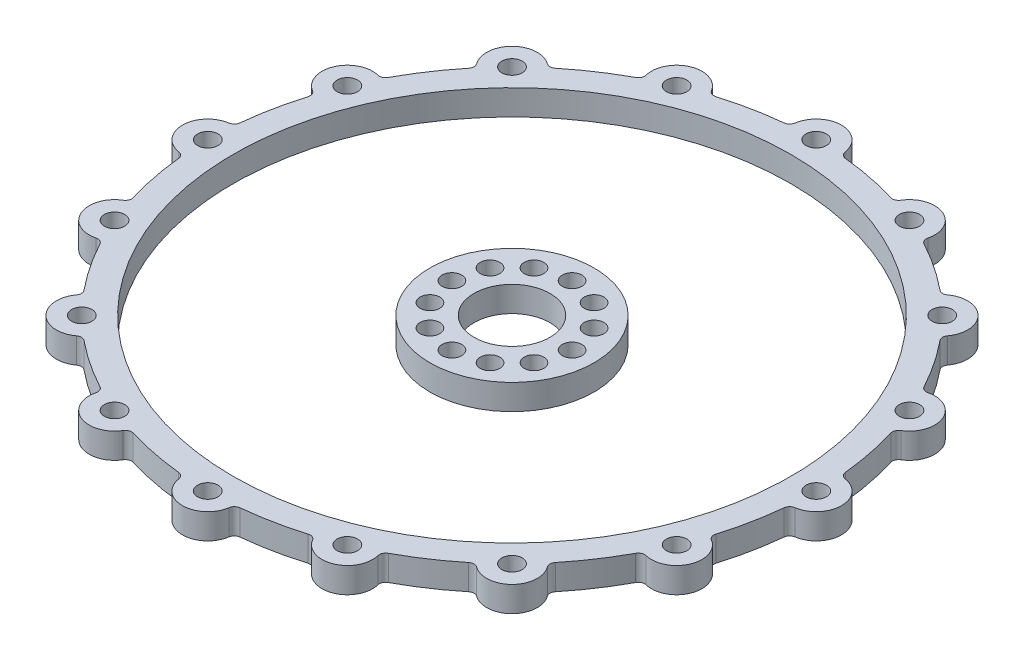
SolidWorks part; units mm, degrees
ref_plane "Front Plane" through (0, 0, 0) normal (0, 0, 1) x (1, 0, 0)
ref_plane "Top Plane" through (0, 0, 0) normal (0, 1, 0) x (1, 0, 0)
ref_plane "Right Plane" through (0, 0, 0) normal (1, 0, 0) x (0, 0, -1)
sketch "Sketch1" plane through (0, 0, 0) normal (0, 1, 0) x (1, 0, 0)
  circle A0 centre (0, 0) radius 76.2
  circle A1 centre (0, 0) radius 9.525
  dimension "D1" = 152.4
  dimension "D2" = 19.05
extrude "Boss-Extrude1" add sketch "Sketch1" along normal blind 6.35
sketch "Sketch2" plane through (0, 6.35, 0) normal (0, 1, 0) x (1, 0, 0)
  circle A0 centre (0, 0) radius 76.2 construction
  arc A1 (6.3445, 75.9354) -> (-6.3445, 75.9354) centre (0, 0) ccw
  arc A2 (6.3445, 75.9354) -> (-6.3445, 75.9354) centre (0, 76.2) ccw
  dimension "D1" = 12.7
extrude "Boss-Extrude3" add sketch "Sketch2" against normal through all
fillet "Fillet1" radius 1.5875 2 edges at (6.3445, 3.175, -75.9354) (-6.3445, 3.175, -75.9354)
hole_wizard "#10 Clearance Hole1" positions "Sketch3" profile "Sketch5" hole size "#10" standard "ANSI Inch"
sketch "Sketch3" plane through (0, 6.35, 0) normal (0, 1, 0) x (1, 0, 0)
  circle A0 centre (0, 0) radius 76.2 construction
  point P4 (0, 76.2)
  dimension "D1" = 152.4
sketch "Sketch5" plane through (0, 6.35, -76.2) normal (1, 0, 0) x (0, 0, 1)
  line L0 (0, 0) -> (0, 8.1378)
  line L1 (0, 8.1378) -> (2.5527, 6.604)
  line L2 (2.5527, 6.604) -> (2.5527, 0)
  line L5 (2.5527, 0) -> (0, 0)
  line L10 (0, 8.1378) -> (-2.5527, 6.604) construction
  line L11 (0, -6.35) -> (0, 107.95) construction
  dimension "Hole Dia." = 5.1054
  dimension "Hole Depth" = 6.604
  dimension "Drill Angle" = 118
pattern_circular "CirPattern1" count 16 over 360 about axis through (0, 6.35, 0) along (0, -1, 0) of "Boss-Extrude3", "Fillet1", "#10 Clearance Hole1" reverse direction yes
hole_wizard "#10 (0.1935) Diameter Hole1" positions "Sketch6" profile "Sketch7" hole size "#10" standard "ANSI Inch"
sketch "Sketch6" plane through (0, 6.35, 0) normal (0, 1, 0) x (1, 0, 0)
  circle A0 centre (0, 0) radius 15.0495
  point P5 (0, 15.0495)
  dimension "D1" = 30.099
sketch "Sketch7" plane through (0, 6.35, -15.0495) normal (1, 0, 0) x (0, 0, 1)
  line L0 (0, 0) -> (0, 13.4146)
  line L1 (0, 13.4146) -> (2.4574, 11.938)
  line L2 (2.4574, 11.938) -> (2.4574, 0)
  line L5 (2.4574, 0) -> (0, 0)
  line L10 (0, 13.4146) -> (-2.4575, 11.938) construction
  line L11 (0, -6.35) -> (0, 107.95) construction
  dimension "Hole Dia." = 4.9149
  dimension "Hole Depth" = 11.938
  dimension "Drill Angle" = 118
pattern_circular "CirPattern2" count 12 over 360 about axis through (0, 6.35, 0) along (0, -1, 0) of "#10 (0.1935) Diameter Hole1" reverse direction yes
sketch "Sketch8" plane through (0, 6.35, 0) normal (0, 1, 0) x (1, 0, 0)
  line L0 (0, 9.525) -> (0, 15.0495) construction
  line L1 (0, 15.0495) -> (0, 20.574) construction
  line L2 (0, 20.574) -> (0, 69.85) construction
  line L3 (17.8176, -10.287) -> (60.4919, -34.925) construction
  line L4 (0, 55.0158) -> (0, 26.924)
  line L5 (15.5136, 52.7832) -> (8.7884, 29.9014)
  line L6 (17.0132, 26.1128) -> (30.0325, 46.0954)
  line L7 (41.8119, 35.7561) -> (23.6862, 20.2556)
  line L8 (28.5094, 12.5914) -> (50.3259, 22.2269)
  line L9 (54.5513, 7.1338) -> (30.903, 4.0413)
  line L10 (30.7603, -5.0131) -> (68.9404, -11.2355)
  line L11 (25.8551, 7.5111) -> (29.9288, 8.6945) construction
  line L12 (54.9463, 2.7641) -> (59.183, 2.9772) construction
  line L13 (59.183, 2.9772) -> (63.4198, 3.1903) construction
  line L14 (17.8499, 20.1565) -> (13.64, 15.4026) construction
  line L15 (54.2448, 33.0114) -> (59.6693, 36.3126) construction
  line L16 (0, 26.924) -> (0, 20.574)
  line L17 (0, 20.574) -> (0, 19.5016)
  circle A0 centre (0, 0) radius 69.85 construction
  arc A1 (6.2782, 77.1525) -> (-6.2782, 77.1525) centre (0, 76.2) ccw construction
  arc A2 (6.2782, 77.1525) -> (-6.2782, 77.1525) centre (0, 76.2) ccw construction
  arc A3 (-6.2782, 77.1525) -> (6.2782, 77.1525) centre (0, 76.2) ccw construction
  arc A4 (6.2782, 77.1525) -> (7.6875, 75.8112) centre (7.8477, 77.3906) ccw construction
  circle A5 centre (0, 0) radius 9.525 construction
  circle A6 centre (0, 0) radius 20.574 construction
  circle A7 centre (0, 0) radius 55.0158 construction
  arc A8 (15.5136, 52.7832) -> (0, 55.0158) centre (7.9174, 55.0158) ccw
  arc A9 (8.7884, 29.9014) -> (17.0132, 26.1128) centre (13.179, 28.6109) ccw
  arc A10 (30.0325, 46.0954) -> (41.8119, 35.7561) centre (36.6662, 41.7733) cw
  arc A11 (28.5094, 12.5914) -> (23.6862, 20.2556) centre (26.6605, 16.7776) cw
  arc A12 (54.5513, 7.1338) -> (50.3259, 22.2269) centre (53.5247, 14.9844) ccw
  arc A13 (30.903, 4.0413) -> (30.7603, -5.0131) centre (31.4964, -0.4964) ccw
  circle A14 centre (0, 0) radius 26.924 construction
  circle A15 centre (0, 0) radius 31.1661 construction
  circle A16 centre (0, 0) radius 63.5 construction
  dimension "D4" = 6.35
  dimension "D1" = 120
sketch "Sketch9" plane through (0, 6.35, 0) normal (0, 1, 0) x (1, 0, 0)
  circle A0 centre (0, 0) radius 69.85
  circle A1 centre (0, 0) radius 20.574
extrude "Cut-Extrude1" cut sketch "Sketch9" against normal through all
sketch "Sketch12" plane through (0, 6.35, 0) normal (0, 1, 0) x (1, 0, 0)
  line L2 (20.574, 0) -> (37.5959, 0) construction
  line L3 (37.5959, 0) -> (46.8121, 23.5035) construction
  line L4 (46.8121, 23.5035) -> (38.1661, 38.1661) construction
  line L5 (38.1661, 38.1661) -> (29.5201, 52.8286) construction
  line L6 (29.5201, 52.8286) -> (3.0118, 58.6502) construction
  line L7 (3.0118, 58.6502) -> (-17.3746, 47.7364) construction
  line L8 (37.5959, 0) -> (28.9498, 14.6625) construction
  line L9 (47.1981, -180.1465) -> (-7.2452, -802.4361) construction
  line L10 (28.9498, 14.6625) -> (20.3038, 29.3251) construction
  line L11 (20.3038, 29.3251) -> (11.6578, 43.9876) construction
  line L12 (11.6578, 43.9876) -> (3.0118, 58.6502) construction
  line L13 (38.1661, 38.1661) -> (0, 0) construction
  line L14 (0, 0) -> (-17.3746, 47.7364) construction
  line L15 (-1000, 0) -> (49000, 0) construction
  line L19 (-68.7888, 12.1293) -> (-52.0256, 9.1735) construction
  line L20 (-52.0256, 9.1735) -> (-37.761, 36.8226) construction
  line L21 (-37.761, 36.8226) -> (-17.3746, 47.7364) construction
  line L22 (29.5201, 52.8286) -> (9.1337, 41.9148) construction
  line L23 (9.1337, 41.9148) -> (-11.2527, 31.0011) construction
  line L24 (-11.2527, 31.0011) -> (-31.6392, 20.0873) construction
  line L26 (-31.6392, 20.0873) -> (-52.0256, 9.1735) construction
  arc A0 (1.1221, 5.0617) -> (-1.7732, 4.8719) centre (0, 0) ccw construction
  arc A1 (1.1221, 5.0617) -> (3.6661, 3.6661) centre (0, 0) cw construction
  circle A3 centre (0, 0) radius 20.574 construction
  circle A4 centre (0, 0) radius 69.85 construction
  spline S0 degree 3 poles (20.574, 0) (37.5959, 0) (46.8121, 23.5035) (38.1661, 38.1661) knots 0 0 0 0 1 1 1 1
  spline S1 degree 3 poles (38.1661, 38.1661) (29.5201, 52.8286) (3.0118, 58.6502) (-17.3746, 47.7364) knots 0 0 0 0 1 1 1 1
  spline S2 degree 3 poles (-68.7888, 12.1293) (-52.0256, 9.1735) (-37.761, 36.8226) (-17.3746, 47.7364) knots 0 0 0 0 1 1 1 1
  point P21 (-69.2835, 8.8777)
  dimension "D1" = 53.975
  dimension "D2" = 50.8
  dimension "D3" = 45
  dimension "D4" = 110
  dimension "D5" = 10
